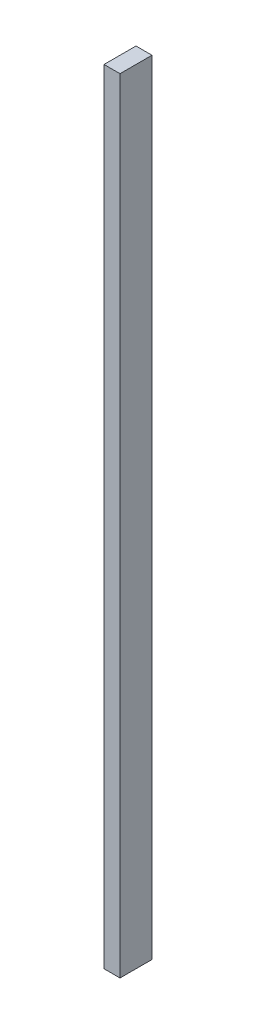
SolidWorks part; units mm, degrees
ref_plane "Front Plane" through (0, 0, 0) normal (0, 0, 1) x (1, 0, 0)
ref_plane "Top Plane" through (0, 0, 0) normal (0, 1, 0) x (1, 0, 0)
ref_plane "Right Plane" through (0, 0, 0) normal (1, 0, 0) x (0, 0, -1)
sketch "Sketch1" plane through (0, 0, 0) normal (0, 1, 0) x (1, 0, 0)
  line L1 (0, 0) -> (-25.4, 0)
  line L2 (0, 0) -> (0, 50.8)
  line L3 (0, 50.8) -> (-25.4, 50.8)
  line L4 (-25.4, 0) -> (-25.4, 50.8)
  dimension "D1" = 25.4
  dimension "D2" = 50.8
extrude "Boss-Extrude1" add sketch "Sketch1" along normal blind 1244.6
